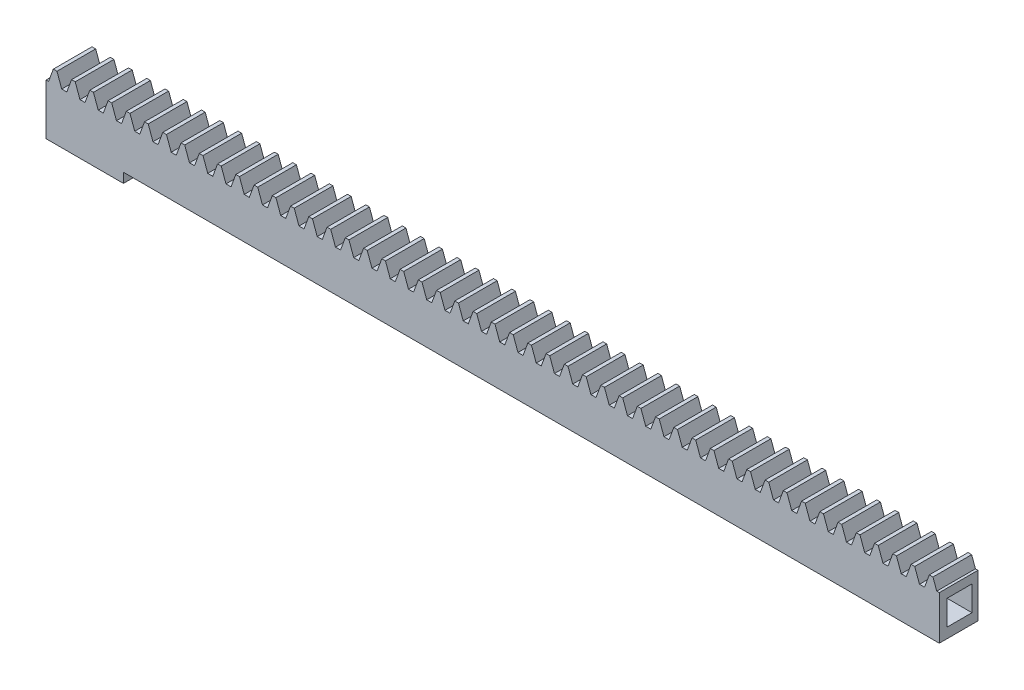
SolidWorks part; units mm, degrees
extrude "Blank" add sketch "BlankSke" against normal blind 10
sketch "BlankSke" plane through (0, 0, 0) normal (0, 0, 1) x (1, 0, 0)
  line L1 (0, 0) -> (230, 0)
  line L2 (0, 0) -> (0, 14)
  line L3 (0, 14) -> (230, 14)
  line L4 (230, 0) -> (230, 14)
  dimension "Length" = 230
ref_plane "Plane1" through (0, 0, 0) normal (0, 0, 1) x (1, 0, 0)
ref_plane "Plane2" through (0, 0, 0) normal (0, 1, 0) x (1, 0, 0)
ref_plane "Plane3" through (0, 0, 0) normal (1, 0, 0) x (0, 0, -1)
other "Configuration Table"
sketch "HoldingSke" plane through (0, 0, 0) normal (0, 1, 0) x (1, 0, 0)
  line L0 (0, 0) -> (0.0928, 0.6602)
  line L1 (-15, 0) -> (100, 0) construction
  line L2 (0, 0) -> (-2.1039, 2.3779)
  line L3 (0, 0) -> (-11.863, 4.5341)
  line L4 (0, 0) -> (5.5511, 6.6156)
  line L5 (0, 0) -> (-23.7986, -8.8762)
  line L6 (0, 0) -> (-10.5278, -7.1032)
  line L9 (-71.009, 38.7566) -> (145.1203, 117.4212)
  line L10 (-76.2, 3.8779) -> (-63.7, 3.8779)
  line L11 (0, 0) -> (-10, 0)
  line L12 (-76.2, 101.6) -> (-76.147, 101.6)
  line L13 (24.9733, 27.94) -> (52.9518, 28.4284)
  line L14 (24.9733, 27.94) -> (24.9743, 27.94)
  line L15 (24.9733, 27.94) -> (100.4006, 29.5858)
  circle A0 centre (0, 0) radius 19.05
  circle A1 centre (0, 0) radius 6.25
  circle A2 centre (0, 0) radius 12.7
  dimension "Num_teeth" = 50
  dimension "Width" = 10
  dimension "Length" = 230
  dimension "Pitch_height" = 12.5
sketch "TooCutSkeIll" plane through (0, 0, 0) normal (0, 0, 1) x (1, 0, 0)
  line L0 (-1.8687, 13.9605) -> (-0.7447, 10.8724)
  line L1 (-0.3914, 10.625) -> (0.3914, 10.625)
  line L2 (0.7447, 10.8724) -> (1.8687, 13.9605)
  line L3 (230, 14) -> (0, 14) construction
  line L4 (0, 0) -> (0, 64.897) construction
  line L5 (-13.208, 12.5) -> (12.954, 12.5) construction
  line L6 (0, 0) -> (230, 0) construction
  line L7 (1.3371, 12.5) -> (1.3371, 48.7463) construction
  line L8 (-1.3371, 12.5) -> (-1.3371, 48.7463) construction
  line L9 (1.9251, 14) -> (1.9251, 14.0254)
  line L10 (-1.9251, 14) -> (-1.9251, 14.0254)
  line L11 (-1.9251, 14.0254) -> (1.9251, 14.0254)
  arc A0 (0.3914, 10.625) -> (0.7447, 10.8724) centre (0.3914, 11.001) ccw
  arc A1 (-0.7447, 10.8724) -> (-0.3914, 10.625) centre (-0.3914, 11.001) ccw
  arc A2 (1.9251, 14) -> (1.8687, 13.9605) centre (1.9251, 13.94) ccw
  arc A3 (-1.8687, 13.9605) -> (-1.9251, 14) centre (-1.9251, 13.94) ccw
  dimension "Addendum_plus" = 1.5254
  dimension "Pitch_height" = 12.5
  dimension "Pressure_angle" = 20
  dimension "Gap_width" = 2.6742
  dimension "Dedendum" = 1.875
extrude "ToothCutIll" [suppressed] cut sketch "TooCutSkeIll" against normal through all
sketch "TooCutSkeSim" plane through (0, 0, 0) normal (0, 0, 1) x (1, 0, 0)
  line L0 (0.6547, 10.625) -> (-0.6547, 10.625)
  line L1 (1.8923, 14.0254) -> (0.6547, 10.625)
  line L2 (0, 17.4625) -> (0, 53.467) construction
  line L3 (1.8923, 14.0254) -> (-1.8923, 14.0254)
  line L6 (-1.8923, 14.0254) -> (-0.6547, 10.625)
  line L9 (-1.3371, 12.5) -> (1.3371, 12.5) construction
  line L10 (0, 0) -> (230, 0) construction
  line L11 (1.3371, 12.5) -> (1.3371, 53.467) construction
  line L12 (-1.3371, 12.5) -> (-1.3371, 53.467) construction
  dimension "Addendum_plus" = 1.5254
  dimension "Pitch_height" = 12.5
  dimension "Pressure_angle" = 20
  dimension "Gap_width" = 2.6742
  dimension "Dedendum" = 1.875
extrude "ToothCutSim" cut sketch "TooCutSkeSim" against normal through all
pattern_linear "TeethCuts" count 50 spacing 4.7124 along (1, 0, 0) of "ToothCutIll", "ToothCutSim"
sketch "Sketch2" plane through (230, 0, 0) normal (1, 0, 0) x (0, 0, -1)
  line L0 (10, 0) -> (10, 11.3185) construction
  line L1 (10, 2.6038) -> (2, 2.6038)
  line L2 (10, 2.6038) -> (10, 9.0538)
  line L3 (10, 9.0538) -> (2, 9.0538)
  line L4 (2, 2.6038) -> (2, 9.0538)
  dimension "D1" = 8
  dimension "D2" = 6.45
extrude "Cut-Extrude2" cut sketch "Sketch2" against normal up to surface (230 mm away) up to face at (0, 5.3125, -5)
sketch "Sketch5" plane through (0, 0, 0) normal (0, -1, 0) x (1, 0, 0)
  line L0 (0, 0) -> (230, 0) construction
  line L1 (0, -10) -> (20, -10)
  line L2 (0, -10) -> (0, 0)
  line L3 (0, 0) -> (20, 0)
  line L4 (20, -10) -> (20, 0)
  dimension "D1" = 20
extrude "Boss-Extrude2" add sketch "Sketch5" along normal blind 2.5
sketch "Sketch7" plane through (0, -2.5, 0) normal (0, -1, 0) x (1, 0, 0)
  circle A0 centre (3.0394, -5.053) radius 2.1
  circle A1 centre (15.7394, -5.053) radius 2.1
  dimension "D2" = 12.7
extrude "Cut-Extrude4" cut sketch "Sketch7" against normal blind 4.57
sketch "Sketch8" plane through (0, 2.6038, 0) normal (0, 1, 0) x (1, 0, 0)
  circle A0 centre (3.0394, 5.053) radius 2.5
  circle A1 centre (15.7394, 5.053) radius 2.5
extrude "Cut-Extrude5" cut sketch "Sketch8" against normal up to surface (0.5338 mm away) up to face at (3.0394, 2.07, -7.153)
sketch "Sketch9" plane through (230, 0, 0) normal (1, 0, 0) x (0, 0, -1)
  line L0 (0, 11.3185) -> (10, 11.3185)
  line L1 (10, 11.3185) -> (10, 9.0538)
  line L2 (10, 9.0538) -> (2, 9.0538)
  line L3 (2, 9.0538) -> (2, 2.6038)
  line L4 (2, 2.6038) -> (10, 2.6038)
  line L5 (10, 2.6038) -> (10, 0)
  line L6 (10, 0) -> (0, 0)
  line L7 (0, 0) -> (0, 11.3185)
extrude "Boss-Extrude3" add sketch "Sketch9" along normal blind 0.655
sketch "Sketch10" plane through (0, 2.6038, 0) normal (0, 1, 0) x (1, 0, 0)
  line L0 (0, 10) -> (230.655, 10) construction
  line L1 (230.655, 10) -> (223.155, 10)
  line L2 (230.655, 10) -> (230.655, 8.45)
  line L3 (230.655, 8.45) -> (223.155, 8.45)
  line L4 (223.155, 10) -> (223.155, 8.45)
  line L5 (1.6515, 10) -> (10.3584, 10)
  line L6 (1.6515, 10) -> (1.6515, 8.45)
  line L7 (1.6515, 8.45) -> (10.3584, 8.45)
  line L8 (10.3584, 10) -> (10.3584, 8.45)
  line L9 (0, 2) -> (230.655, 2) construction
  dimension "D1" = 6.45
  dimension "D2" = 7.5
  dimension "D3" = 6.45
extrude "Boss-Extrude4" add sketch "Sketch10" along normal up to surface (6.45 mm away) up to face at (115.3275, 9.0538, -6)
sketch "Sketch11" plane through (1.6515, 0, 0) normal (-1, 0, 0) x (0, 0, 1)
  line L0 (-10, 2.6038) -> (-8.45, 3.1038)
  line L1 (-8.45, 9.0538) -> (-8.45, 2.6038) construction
  line L2 (-8.45, 3.1038) -> (-8.45, 9.0538)
  line L3 (-10, 9.0538) -> (-2, 9.0538) construction
  line L4 (-8.45, 9.0538) -> (-10, 9.0538)
  line L5 (-10, 9.0538) -> (-10, 2.6038)
  line L6 (-2, 2.6038) -> (-10, 2.6038) construction
  dimension "D1" = 0.5
extrude "Cut-Extrude6" cut sketch "Sketch11" against normal up to surface (8.7069 mm away) up to face at (10.3584, 5.8288, -9.225)
equation "' \"Module@HoldingSke\" = 6.35"
equation "' \"Num_teeth@HoldingSke\" = 12"
equation "' \"Ap@HoldingSke\" =  20"
equation "' \"Ap@HoldingSke\" = 20"
equation "' \"Width@HoldingSke\" = 0.25 * 25.4"
equation "' \"Show_teeth@HoldingSke\" = 500"
equation "' \"Backlash@HoldingSke\" = 0.009 * 25.4"
equation "' \"Addendum_fac@HoldingSke\" = 1.0"
equation "' \"Dedendum_fac@HoldingSke\" = 1.25"
equation "' \"Dedendum_add@HoldingSke\" = 0.00005 * 25.4"
equation "' \"Clearance_fac@HoldingSke\" = 0.25"
equation "' \"Pitch_height@HoldingSke\" = 1 * 25.4"
equation "' \"Length@HoldingSke\" = 4.71 * 25.4"
equation "\"Pitch@HoldingSke\" = 1 / \"Module@HoldingSke\""
equation "\"MPH@HoldingSke\" = \"Dedendum_fac@HoldingSke\" / \"Pitch@HoldingSke\" + 2 * \"Dedendum_add@HoldingSke\" + 0.002 * 25.4"
equation "\"MPH@HoldingSke\" = ((sgn( \"MPH@HoldingSke\" - \"Pitch_height@HoldingSke\")+1)*( \"MPH@HoldingSke\" - \"Pitch_height@HoldingSke\"))/2 + \"Pitch_height@HoldingSke\""
equation "\"Blank_height@BlankSke\" = \"Pitch_height@HoldingSke\" + \"Addendum_fac@HoldingSke\"  / \"Pitch@HoldingSke\" "
equation "\"Length@BlankSke\" =  \"Length@HoldingSke\""
equation "\"Face_width@Blank\" = \"Width@HoldingSke\""
equation "\"Pressure_angle@TooCutSkeIll\" = \"Ap@HoldingSke\""
equation "\"Addendum_plus@TooCutSkeIll\" =  \"Addendum_fac@HoldingSke\"  / \"Pitch@HoldingSke\" + 0.001 *25.4"
equation "\"Dedendum@TooCutSkeIll\" = \"Dedendum_fac@HoldingSke\"  / \"Pitch@HoldingSke\""
equation "\"Pitch_height@TooCutSkeIll\" =  \"MPH@HoldingSke\""
equation "\"Gap_width@TooCutSkeIll\" = 3.14159265 / 2 / \"Pitch@HoldingSke\" + 6 * \"Backlash@HoldingSke\""
equation "\"Pressure_angle@TooCutSkeSim\" = \"Ap@HoldingSke\""
equation "\"Addendum_plus@TooCutSkeSim\" =  \"Addendum_fac@HoldingSke\"  / \"Pitch@HoldingSke\" + 0.001 * 25.4"
equation "\"Dedendum@TooCutSkeSim\" = \"Dedendum_fac@HoldingSke\"  / \"Pitch@HoldingSke\""
equation "\"Pitch_height@TooCutSkeSim\" =  \"MPH@HoldingSke\""
equation "\"Gap_width@TooCutSkeSim\" = 3.14159265 / 2 / \"Pitch@HoldingSke\" + 6 * \"Backlash@HoldingSke\""
equation "\"Root_fillet@TooCutSkeIll\" = \"Clearance_fac@HoldingSke\" / \"Pitch@HoldingSke\" + \"Dedendum_add@HoldingSke\""
equation "\"Break_rad@TooCutSkeIll\" = 0.02 / \"Pitch@HoldingSke\" * 2"
equation "\"Linear_pitch@TeethCuts\" = 3.14159265 / \"Pitch@HoldingSke\""
equation "\"Num_teeth@HoldingSke\" = int( ( \"Length@HoldingSke\" + 0 ) / (3.14159265 / \"Pitch@HoldingSke\")) + 0.9999  + 1"
equation " \"Num_teeth@TeethCuts\" = int( \"Show_teeth@HoldingSke\" ) + 1"
equation " \"Num_teeth@TeethCuts\" = ((sgn( \"Num_teeth@TeethCuts\" - \"Num_teeth@HoldingSke\" )-1)*( \"Num_teeth@TeethCuts\" - \"Num_teeth@HoldingSke\" ))/-2+ \"Num_teeth@HoldingSke\""
equation " \"Num_teeth@TeethCuts\" = ((sgn( \"Num_teeth@TeethCuts\" - 2.0)+1)*( \"Num_teeth@TeethCuts\" - 2.0))/2 +2.0"
